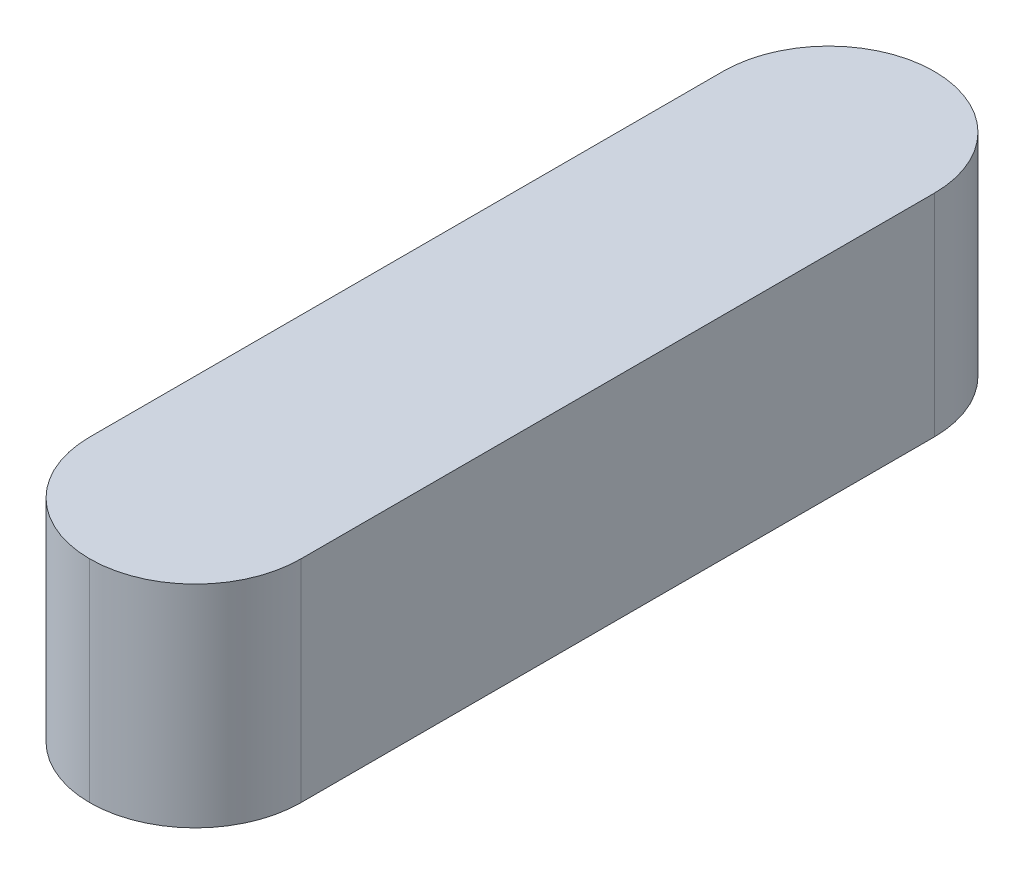
SolidWorks part; units mm, degrees
ref_plane "Front Plane" through (0, 0, 0) normal (0, 0, 1) x (1, 0, 0)
ref_plane "Top Plane" through (0, 0, 0) normal (0, 1, 0) x (1, 0, 0)
ref_plane "Right Plane" through (0, 0, 0) normal (1, 0, 0) x (0, 0, -1)
sketch "Sketch1" plane through (0, 0, 0) normal (0, 0, 1) x (1, 0, 0)
  line L1 (0, 0) -> (4, 0)
  line L2 (0, 0) -> (0, 4)
  line L3 (0, 4) -> (4, 4)
  line L4 (4, 0) -> (4, 4)
  dimension "D1" = 4
  dimension "D2" = 4
extrude "KeyExtrusion" add sketch "Sketch1" along normal blind 16
fillet "EndRadii" radius 2 4 edges at (0, 2, 0) (4, 2, 0) (0, 2, 16) (4, 2, 16)
